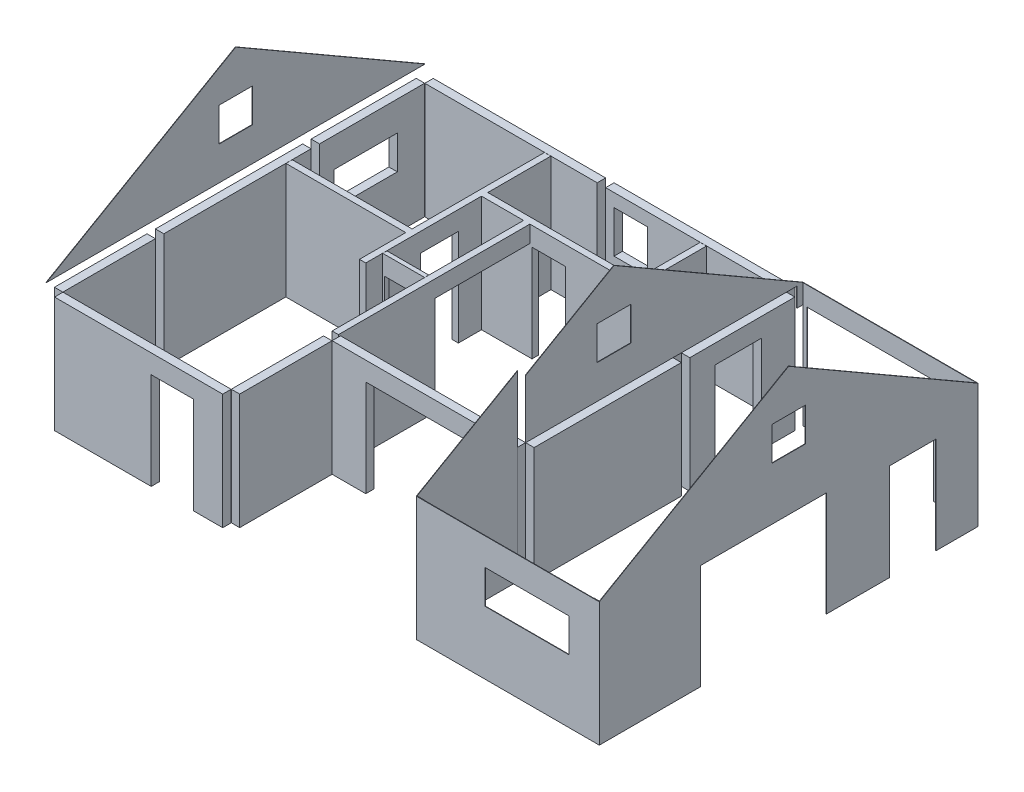
SolidWorks part; units mm, degrees
ref_plane "Спереди" through (0, 0, 0) normal (0, 0, 1) x (1, 0, 0)
ref_plane "Сверху" through (0, 0, 0) normal (0, 1, 0) x (1, 0, 0)
ref_plane "Справа" through (0, 0, 0) normal (1, 0, 0) x (0, 0, -1)
sketch "Эскиз1" plane through (0, 0, 0) normal (0, 1, 0) x (1, 0, 0)
  line L0 (9000, -6600) -> (4400, -6600) construction
  line L1 (0, 0) -> (9000, 0) construction
  line L2 (0, 0) -> (0, -8800) construction
  line L3 (0, -9000) -> (4400, -9000) construction
  line L4 (9000, 0) -> (9000, -6600) construction
  line L5 (4400, -6600) -> (4400, -9000) construction
  line L6 (8800, -203) -> (9000, -203)
  line L7 (203, 0) -> (4300, 0)
  line L8 (203, 0) -> (203, -200)
  line L9 (203, -200) -> (4300, -200)
  line L12 (0, -200) -> (0, -2700)
  line L14 (200, -200) -> (200, -2700)
  line L15 (203, -9000) -> (2500, -9000)
  line L16 (203, -9000) -> (203, -8800)
  line L17 (203, -8800) -> (2500, -8800)
  line L19 (4400, -8797) -> (4200, -8797)
  line L20 (4400, -8797) -> (4400, -6603)
  line L22 (4200, -8797) -> (4200, -6603)
  line L24 (9000, -203) -> (9000, -1000)
  line L26 (8800, -203) -> (8800, -1000)
  line L27 (8797, -6600) -> (7597, -6600)
  line L28 (8797, -6600) -> (8797, -6400)
  line L29 (8797, -6400) -> (7597, -6400)
  line L31 (2500, -8800) -> (2500, -9000)
  line L32 (3500, -8800) -> (3500, -9000)
  line L33 (3500, -8800) -> (4200, -8800)
  line L34 (3500, -9000) -> (4200, -9000)
  line L35 (5597, -6400) -> (5597, -6600)
  line L36 (7597, -6400) -> (7597, -6600)
  line L37 (5597, -6400) -> (4400, -6400)
  line L38 (5597, -6600) -> (4400, -6600)
  line L39 (8800, -1000) -> (9000, -1000)
  line L41 (8800, -2100) -> (9000, -2100)
  line L42 (8800, -2100) -> (8800, -2700)
  line L43 (9000, -2100) -> (9000, -2700)
  line L47 (4200, -6400) -> (4350, -6400)
  line L83 (4200, -6603) -> (4400, -6603)
  line L92 (4200, -4100) -> (4350, -4100)
  line L93 (4200, -4100) -> (4200, -6400)
  line L94 (4350, -4100) -> (4350, -6400)
  line L100 (200, -8800) -> (0, -8800)
  line L101 (4200, -8800) -> (4200, -9000)
  line L102 (4400, -6400) -> (4400, -6600)
  line L103 (8800, -6400) -> (9000, -6400)
  line L104 (0, -200) -> (200, -200)
  line L108 (0, -4500) -> (0, -6400)
  line L109 (200, -4500) -> (200, -6400)
  line L110 (8800, 0) -> (8800, -200)
  line L111 (4300, 0) -> (4300, -200)
  line L113 (4500, 0) -> (4500, -200)
  line L114 (4500, 0) -> (8800, 0)
  line L115 (4500, -200) -> (8800, -200)
  line L116 (0, -9000) -> (0, -8800) construction
  line L117 (-6170.9643, 0) -> (12200, 0) construction
  line L118 (0, 1882.3698) -> (0, -11726.3327) construction
  line L119 (-6170.9643, -4500) -> (10764.3505, -4500) construction
  line L120 (1000, -4500) -> (2250, -4500) construction
  line L121 (-6170.9643, -9000) -> (12200, -9000) construction
  line L122 (1000, -4500) -> (1000, -4600) construction
  line L123 (1000, -4600) -> (2250, -4600) construction
  line L124 (2250, -4500) -> (2250, -4600) construction
  line L125 (1000, -4500) -> (2250, -4600) construction
  line L126 (1000, -4600) -> (2250, -4500) construction
  line L131 (0, -2700) -> (200, -2700)
  line L132 (0, -2900) -> (0, -4500)
  line L137 (3050, -203) -> (3200, -203)
  line L138 (3050, -203) -> (3050, -2400)
  line L139 (3050, -2400) -> (3200, -2400)
  line L140 (3200, -203) -> (3200, -1700)
  line L141 (3050, -203) -> (3200, -2400) construction
  line L142 (3050, -2400) -> (3200, -203) construction
  line L143 (3050, -3300) -> (3200, -3300)
  line L144 (3050, -3300) -> (3050, -3350)
  line L145 (3050, -4600) -> (3200, -4600)
  line L146 (3200, -3300) -> (3200, -4600)
  line L147 (3050, -3300) -> (3200, -4600) construction
  line L148 (3050, -4600) -> (3200, -3300) construction
  line L149 (4150, -4100) -> (4197, -4100)
  line L150 (4150, -4100) -> (4150, -4200)
  line L151 (4150, -4200) -> (4197, -4200)
  line L152 (4197, -4100) -> (4197, -4200)
  line L153 (4150, -4100) -> (4197, -4200) construction
  line L154 (4150, -4200) -> (4197, -4100) construction
  line L155 (203, -3350) -> (3050, -3350)
  line L156 (203, -3350) -> (203, -3500)
  line L157 (203, -3500) -> (3050, -3500)
  line L159 (203, -3350) -> (3050, -3500) construction
  line L160 (203, -3500) -> (3050, -3350) construction
  line L161 (6400, -3500) -> (8800, -3500) construction
  line L162 (4400, 2182.3698) -> (4400, -11426.3327) construction
  line L163 (5200, -1700) -> (6750, -1700)
  line L164 (9000, 2182.3698) -> (9000, -11265.4622) construction
  line L165 (5200, -1700) -> (5200, -1850)
  line L166 (5200, -1850) -> (6900, -1850)
  line L167 (6900, -1700) -> (6900, -1850)
  line L168 (5200, -1700) -> (6900, -1850) construction
  line L169 (5200, -1850) -> (6900, -1700) construction
  line L170 (5800, -2800) -> (8797, -2800) construction
  line L171 (5800, -2800) -> (5800, -2900) construction
  line L172 (5800, -2900) -> (8797, -2900) construction
  line L173 (8797, -2800) -> (8797, -2900) construction
  line L174 (5800, -2800) -> (8797, -2900) construction
  line L175 (5800, -2900) -> (8797, -2800) construction
  line L176 (6750, -203) -> (6900, -203)
  line L177 (6750, -203) -> (6750, -1700)
  line L179 (6900, -203) -> (6900, -1700)
  line L180 (6750, -203) -> (6900, -1700) construction
  line L181 (6750, -1700) -> (6900, -203) construction
  line L186 (3200, -1700) -> (4400, -1700)
  line L188 (3200, -1850) -> (4400, -1850)
  line L189 (4400, -1700) -> (4400, -1850)
  line L190 (3200, -1700) -> (4400, -1850) construction
  line L191 (3200, -1850) -> (4400, -1700) construction
  line L192 (5800, -2900) -> (6400, -2900) construction
  line L193 (5800, -2900) -> (5800, -3500) construction
  line L194 (5800, -3500) -> (6400, -3500) construction
  line L195 (6400, -2900) -> (6400, -3500) construction
  line L196 (5800, -2900) -> (6400, -3500) construction
  line L197 (5800, -3500) -> (6400, -2900) construction
  line L198 (12200, 0) -> (12200, -9000) construction
  line L199 (5350, -4400) -> (5800, -3500) construction
  line L204 (3203, -4100) -> (3250, -4100)
  line L205 (3203, -4100) -> (3203, -4200)
  line L206 (3203, -4200) -> (3250, -4200)
  line L207 (3250, -4100) -> (3250, -4200)
  line L208 (3203, -4100) -> (3250, -4200) construction
  line L209 (3203, -4200) -> (3250, -4100) construction
  line L210 (4350, -4400) -> (5350, -4400) construction
  line L211 (4350, -4400) -> (4350, -6400) construction
  line L212 (4350, -6400) -> (5350, -6400) construction
  line L213 (5350, -4400) -> (5350, -6400) construction
  line L214 (4350, -4400) -> (5350, -6400) construction
  line L215 (4350, -6400) -> (5350, -4400) construction
  line L216 (3200, -1850) -> (3200, -2400)
  line L217 (0, -2900) -> (200, -2900)
  line L218 (200, -2900) -> (200, -4500)
  line L219 (0, -6400) -> (200, -6400)
  line L220 (0, -6600) -> (0, -8800)
  line L221 (0, -6600) -> (200, -6600)
  line L222 (200, -6600) -> (200, -8800)
  line L223 (3050, -3500) -> (3050, -4600)
  line L224 (8800, -2700) -> (9000, -2700)
  line L225 (8800, -2900) -> (8800, -6400)
  line L226 (8800, -2900) -> (9000, -2900)
  line L227 (9000, -2900) -> (9000, -6400)
  point P14 (3226.5, -4150)
  point P17 (7298.5, -2850)
  point P41 (1625, -4550)
  point P52 (3125, -1301.5)
  point P62 (3125, -3950)
  point P67 (4173.5, -4150)
  point P72 (1626.5, -3425)
  point P103 (3800, -1775)
  point P104 (6825, -951.5)
  point P105 (4150, -4150)
  point P108 (6050, -1775)
  point P120 (6750, -951.5)
  point P122 (6100, -3200)
  point P127 (4850, -5400)
  dimension "D2" = 6600
  dimension "D3" = 9000
  dimension "D4" = 200
  dimension "D5" = 3
  dimension "D6" = 3
  dimension "D7" = 3
  dimension "D8" = 9000
  dimension "D9" = 200
  dimension "D10" = 3
  dimension "D11" = 3
  dimension "D12" = 700
  dimension "D13" = 50
  dimension "D14" = 4500
  dimension "D15" = 4000
  dimension "D16" = 100
  dimension "D17" = 800
  dimension "D18" = 4400
  dimension "D19" = 4600
  dimension "D20" = 1000
  dimension "D21" = 800
  dimension "D22" = 2000
  dimension "D23" = 1200
  dimension "D24" = 1100
  dimension "D25" = 3
  dimension "D26" = 200
  dimension "D27" = 1000
  dimension "D29" = 200
  dimension "D30" = 4500
  dimension "D31" = 3
  dimension "D32" = 200
  dimension "D33" = 3
  dimension "D34" = 900
  dimension "D35" = 3
  dimension "D36" = 900
  dimension "D37" = 50
  dimension "D38" = 150
  dimension "D39" = 100
  dimension "D40" = 3
  dimension "D41" = 2850
  dimension "D42" = 3150
  dimension "D43" = 1250
  dimension "D44" = 200
  dimension "D46" = 3550
  dimension "D47" = 1500
  dimension "D48" = 800
  dimension "D49" = 1900
  dimension "D50" = 950
  dimension "D51" = 3
  dimension "D53" = 800
  dimension "D54" = 3
  dimension "D55" = 4450
  dimension "D56" = 3500
  dimension "D57" = 2400
  dimension "D58" = 3000
  dimension "D59" = 1400
  dimension "D60" = 2650
  dimension "D61" = 600
  dimension "D63" = 2900
  dimension "D64" = 2300
  dimension "D65" = 1247
  dimension "D66" = 3200
  dimension "D67" = 2000
  dimension "D68" = 1000
  dimension "D72" = 200
extrude "Бобышка-Вытянуть3" add sketch "Эскиз1" along normal blind 2750 contours L155 | L42 L103 L43 L41 | L26 L39 L24 L6 | L113 L115 L110 L114 | L216 L188 L189 L186 L140 L137 L138 L139 | L179 L176 L177 L163 L165 L166 L167 | L157 L223 L145 L146 L143 L144 L155 L156 | L108 L219 L109 L218 L217 L132 | L222 L221 L220 L100 | L144 L145 L146 L143 | L140 L139 L138 L137 | L27 L36 L29 L28 | L8 L9 L111 L7 | L14 L131 L12 L104 | L100 L108 L132 L217 L218 L109 | L47 L94 L92 L93 | L35 L38 L102 L37 | L171 L172 L173 L170 | L19 L22 L83 L20 | L32 L34 L101 L33 | L15 L31 L17 L16 | L122 L120 L124 L123 | L205 L204 L207 L206 | L150 L149 L152 L151 | L165 L163 L167 L166 | L103 L227 L226 L225 region at (8900, 0, 601.5) region at (8900, 0, 2400) region at (100, 0, 7700) region at (100, 0, 4650) region at (6650, 0, 100) region at (3125, 0, 228.7863) region at (3125, 0, 3332.668) region at (5975, 0, 1723.6698)
sketch "Эскиз2" plane through (0, 0, 0) normal (-1, 0, 0) x (0, 0, 1)
  line L2 (850, 1250) -> (2350, 1250)
  line L3 (850, 1250) -> (850, 2050)
  line L4 (850, 2050) -> (2350, 2050)
  line L5 (2350, 1250) -> (2350, 2050)
  line L7 (200, 0) -> (2700, 0) construction
  line L8 (3350, 2750) -> (3350, 0) construction
  dimension "D1" = 1500
  dimension "D2" = 800
  dimension "D3" = 1250
  dimension "D4" = 1000
extrude "Вырез-Вытянуть2" cut sketch "Эскиз2" against normal blind 250
sketch "Эскиз3" plane through (0, 0, 0) normal (0, 0, -1) x (-1, 0, 0)
  line L0 (-4500, 0) -> (-8800, 0) construction
  line L8 (-5500, 2440) -> (-4700, 2440)
  line L9 (-5500, 2440) -> (-5500, 1440)
  line L10 (-5500, 1440) -> (-4700, 1440)
  line L11 (-4700, 2440) -> (-4700, 1440)
  line L15 (-4500, 2750) -> (-4500, 0) construction
  dimension "D1" = 200
  dimension "D2" = 2440
  dimension "D3" = 800
  dimension "D4" = 1000
  dimension "D5" = 1440
extrude "Вырез-Вытянуть3" cut sketch "Эскиз3" against normal blind 593
sketch "Эскиз4" plane through (0, 2750, 0) normal (0, 1, 0) x (1, 0, 0)
  line L6 (3203, -4100) -> (3250, -4100) construction
  line L7 (3226.5, -4100) -> (4173.5, -4100)
  line L8 (3226.5, -4100) -> (3226.5, -4200)
  line L9 (3226.5, -4200) -> (4173.5, -4200)
  line L10 (4173.5, -4100) -> (4173.5, -4200)
  line L11 (4150, -4200) -> (4197, -4200) construction
  line L13 (3050, -2346.4504) -> (3200, -2346.4504)
  line L14 (3050, -2346.4504) -> (3050, -3325)
  line L15 (3050, -3325) -> (3200, -3325)
  line L16 (3200, -2346.4504) -> (3200, -3325)
  line L19 (4249.5007, -1700) -> (5402.0861, -1700)
  line L20 (4249.5007, -1700) -> (4249.5007, -1850)
  line L21 (4249.5007, -1850) -> (5402.0861, -1850)
  line L22 (5402.0861, -1700) -> (5402.0861, -1850)
  line L24 (5200, -1850) -> (6900, -1850) construction
  line L29 (3050, -203) -> (3050, -2400) construction
  line L30 (5597, -6400) -> (4400, -6400) construction
  line L31 (5423.0031, -6400) -> (7690.4362, -6400)
  line L32 (5423.0031, -6400) -> (5423.0031, -6600)
  line L33 (5423.0031, -6600) -> (7690.4362, -6600)
  line L34 (7690.4362, -6400) -> (7690.4362, -6600)
  line L35 (8797, -6600) -> (7597, -6600) construction
  line L36 (8800, -203) -> (8800, -1000) construction
  line L37 (8800, -900.8258) -> (9000, -900.8258)
  line L38 (8800, -900.8258) -> (8800, -2153.976)
  line L39 (8800, -2153.976) -> (9000, -2153.976)
  line L40 (9000, -900.8258) -> (9000, -2153.976)
  line L41 (9000, -2100) -> (9000, -2700) construction
  line L42 (3500, -9000) -> (4200, -9000) construction
  line L43 (2379.0159, -8797) -> (3597.5552, -8797)
  line L44 (2379.0159, -8797) -> (2379.0159, -9000)
  line L45 (2379.0159, -9000) -> (3597.5552, -9000)
  line L46 (3597.5552, -8797) -> (3597.5552, -9000)
  line L47 (3200, -1850) -> (3200, -2400) construction
  line L48 (3200, -1700) -> (4400, -1700) construction
extrude "Бобышка-Вытянуть4" add sketch "Эскиз4" against normal offset from surface (450 mm away) 2300 up to face at (8900, 0, 601.5)
ref_plane "Плоскость1" through (13000, 0, 0) normal (1, 0, 0) x (0, 0, -1)
sketch "Эскиз5" plane through (13000, 0, 0) normal (1, 0, 0) x (0, 0, -1)
  line L0 (-4500, 5721.2813) -> (-4500, -150) construction
  line L1 (-6600, -150) -> (0, -150) construction
  line L2 (-4500, 5548.0762) -> (-9000, 2950)
  line L3 (-9000, 2950) -> (-9000, 0)
  line L5 (0, 2950) -> (0, 0)
  line L6 (-4500, 5548.0762) -> (0, 2950)
  line L7 (-8800, 0) -> (-9000, 0) construction
  line L8 (-9000, 0) -> (-8750, 0) construction
  line L9 (-9000, 0) -> (0, 0)
extrude "Бобышка-Вытянуть5" add sketch "Эскиз5" along normal blind 150 separate body
sketch "Эскиз6" plane through (13000, 0, 0) normal (1, 0, 0) x (0, 0, -1)
  line L0 (-9000, 0) -> (0, 0) construction
  line L1 (-1000, 2300) -> (-2100, 2300)
  line L2 (-1000, 2300) -> (-1000, 0)
  line L3 (-1000, 0) -> (-2100, 0)
  line L4 (-2100, 2300) -> (-2100, 0)
  line L5 (0, 2494.3376) -> (50, 2494.3376) construction
  line L6 (-6600, -150) -> (-3600, -150)
  line L7 (-6600, -150) -> (-6600, 2494.3376)
  line L8 (-6600, 2494.3376) -> (-3600, 2494.3376)
  line L9 (-3600, -150) -> (-3600, 2494.3376)
  dimension "D1" = 3000
  dimension "D2" = 1100
extrude "Вырез-Вытянуть5" cut sketch "Эскиз6" along normal blind 670
sketch "Эскиз8" plane through (0, 0, 0) normal (-1, 0, 0) x (0, 0, 1)
  line L0 (4500, 5548.0762) -> (0, 2950)
  line L1 (0, 2950) -> (9000, 2950)
  line L2 (9000, 2950) -> (4500, 5548.0762)
  line L3 (4500, 5548.0762) -> (4500, 2950) construction
  line L4 (2350, 1250) -> (2350, 2050) construction
  line L5 (4100, 4550) -> (4900, 4550)
  line L6 (4100, 4550) -> (4100, 3750)
  line L7 (4100, 3750) -> (4900, 3750)
  line L8 (4900, 4550) -> (4900, 3750)
  dimension "D1" = 800
extrude "Бобышка-Вытянуть8" add sketch "Эскиз8" against normal blind 10 separate body
sketch "Эскиз9" plane through (9000, 0, 0) normal (1, 0, 0) x (0, 0, -1)
  line L0 (-6600, 0) -> (-6600, 2950)
  line L1 (-6600, 2750) -> (-6600, 0) construction
  line L2 (-6600, 2950) -> (0, 2950)
  line L3 (0, 2950) -> (-4500, 5548.0762)
  line L4 (-4500, 5548.0762) -> (-9000, 2950)
  line L5 (-9000, 2950) -> (-9000, 0)
  line L6 (-9000, 0) -> (-6600, 0)
extrude "Бобышка-Вытянуть9" add sketch "Эскиз9" against normal blind 200 separate body
sketch "Эскиз10" plane through (0, 0, 0) normal (0, -1, 0) x (1, 0, 0)
  line L0 (13000, 9000) -> (13000, 6600) construction
  line L1 (9000, 9000) -> (13000, 9000)
  line L2 (9000, 9000) -> (9000, 8850)
  line L3 (9000, 8850) -> (13000, 8850)
  line L4 (13000, 9000) -> (13000, 8850)
  line L5 (13150, 9000) -> (13000, 9000) construction
  line L6 (9000, 6600) -> (9000, 0) construction
  line L7 (13000, 0) -> (12100, 0)
  line L8 (13000, 0) -> (13000, 150)
  line L9 (13000, 150) -> (12100, 150)
  line L10 (12100, 0) -> (12100, 150)
  line L11 (9000, 150) -> (9100, 150)
  line L12 (9000, 150) -> (9000, 0)
  line L13 (9000, 0) -> (9100, 0)
  line L14 (9100, 150) -> (9100, 0)
extrude "Бобышка-Вытянуть10" add sketch "Эскиз10" against normal up to vertex (2950 mm away) up to point (9000, 2950, 9000)
sketch "Эскиз11" plane through (0, 0, 6400) normal (0, 0, -1) x (-1, 0, 0)
  line L1 (-7597, 2300) -> (-5200, 2300)
  line L2 (-7597, 2300) -> (-7597, -335.5255)
  line L3 (-7597, -335.5255) -> (-5200, -335.5255)
  line L4 (-5200, 2300) -> (-5200, -335.5255)
  line L6 (-2500, 2300) -> (-3500, 2300)
  line L7 (-2500, 2300) -> (-2500, -123.1481)
  line L8 (-2500, -123.1481) -> (-3500, -123.1481)
  line L9 (-3500, 2300) -> (-3500, -123.1481)
  line L11 (-10431.0972, 2300) -> (-12431.0972, 2300)
  line L12 (-10431.0972, 2300) -> (-10431.0972, 1500)
  line L13 (-10431.0972, 1500) -> (-12431.0972, 1500)
  line L14 (-12431.0972, 2300) -> (-12431.0972, 1500)
  dimension "D1" = 2000
  dimension "D2" = 800
  dimension "D3" = 2397
extrude "Вырез-Вытянуть6" cut sketch "Эскиз11" against normal blind 5123
sketch "Эскиз12" plane through (0, 0, 0) normal (-1, 0, 0) x (0, 0, 1)
  line L0 (2424.8711, 2950) -> (2424.8711, 4350) construction
  line L1 (0, 2950) -> (9000, 2950) construction
  line L2 (4500, 5548.0762) -> (0, 2950) construction
  line L3 (2424.8711, 4350) -> (3290.8965, 4850) construction
  line L4 (3290.8965, 4850) -> (5709.1035, 4850) construction
  line L5 (9000, 2950) -> (4500, 5548.0762) construction
  line L6 (5709.1035, 4850) -> (6575.1289, 4350) construction
  line L7 (6575.1289, 4350) -> (6575.1289, 2950) construction
  line L8 (4500, 5548.0762) -> (4500, 4850) construction
  dimension "D1" = 1900
  dimension "D2" = 2418.2069
  dimension "D3" = 1400
  dimension "D4" = 4150.2577
extrude "Вырез-Вытянуть7" cut sketch "Эскиз8<2>" against normal blind 16606 contours L5 L8 L7 L6
sketch "Эскиз8<2>" plane through (0, 0, 0) normal (-1, 0, 0) x (0, 0, 1) same geometry as "Эскиз8"
sketch "Эскиз13" plane through (0, 0, 0) normal (-1, 0, 0) x (0, 0, 1)
  line L0 (4500, 5548.0762) -> (0, 2950)
  line L1 (0, 2950) -> (0, 0)
  line L2 (0, 0) -> (9000, 0)
  line L3 (9000, 2950) -> (9000, 0) construction
  line L4 (4500, 5548.0762) -> (9000, 2950)
  line L5 (9000, 2950) -> (9000, 0)
  line L7 (4100, 4550) -> (4900, 4550)
  line L8 (4100, 4550) -> (4100, 3750)
  line L9 (4100, 3750) -> (4900, 3750)
  line L10 (4900, 4550) -> (4900, 3750)
  line L11 (850, 2050) -> (2350, 2050)
  line L12 (850, 2050) -> (850, 1250)
  line L13 (850, 1250) -> (2350, 1250)
  line L14 (2350, 2050) -> (2350, 1250)
sketch "Эскиз16" plane through (13150, 0, 0) normal (1, 0, 0) x (0, 0, -1)
  line L0 (-150, 2950) -> (-150, 0) construction
  line L1 (0, 2950) -> (-150, 2950)
  line L2 (0, 2950) -> (0, 2494.3376)
  line L3 (0, 2494.3376) -> (-150, 2494.3376)
  line L4 (-150, 2950) -> (-150, 2494.3376)
  line L5 (-3600, 2494.3376) -> (-6600, 2494.3376) construction
extrude "Бобышка-Вытянуть16" add sketch "Эскиз16" against normal blind 4160
sketch "Эскиз17" plane through (0, 0, 4100) normal (0, 0, -1) x (-1, 0, 0)
  line L0 (-4200, 2750) -> (-4200, 0) construction
  line L1 (-4350, 2750) -> (-4200, 2750)
  line L2 (-4350, 2750) -> (-4350, 2350)
  line L3 (-4350, 2350) -> (-4200, 2350)
  line L4 (-4200, 2750) -> (-4200, 2350)
  dimension "D1" = 400
extrude "Бобышка-Вытянуть17" add sketch "Эскиз17" along normal up to surface (2250 mm away) up to face at (4925, 1262.5, 1850)
sketch "Эскиз18" plane through (0, 2750, 0) normal (0, 1, 0) x (1, 0, 0)
  line L0 (9000, -4500) -> (9000, -9000) construction
  line L1 (8644.5298, 46.0605) -> (8990, 46.0605)
  line L2 (8644.5298, 46.0605) -> (8644.5298, -6600)
  line L3 (8644.5298, -6600) -> (8990, -6600)
  line L4 (8990, 46.0605) -> (8990, -6600)
  line L5 (8797, -6600) -> (4400, -6600) construction
  line L6 (13000, -9000) -> (9000, -9000) construction
  line L7 (9392.4652, -10) -> (13140, -10)
  line L8 (9392.4652, -10) -> (9392.4652, -8990)
  line L9 (9392.4652, -8990) -> (13140, -8990)
  line L10 (13140, -10) -> (13140, -8990)
  line L11 (13150, -4500) -> (13150, -9000) construction
  line L12 (9000, 0) -> (13000, 0) construction
  dimension "D1" = 10
  dimension "D2" = 10
  dimension "D3" = 10
  dimension "D4" = 10
extrude "Вырез-Вытянуть8" cut sketch "Эскиз18" along normal blind 5414
sketch "Эскиз19" plane through (0, 0, 0) normal (0, -1, 0) x (1, 0, 0)
  line L0 (8990, 6600) -> (8800, 6600) construction
  line L1 (8810, 6600) -> (11709.562, 6600)
  line L2 (8810, 6600) -> (8810, 8990)
  line L3 (8810, 8990) -> (13140, 8990)
  line L4 (13140, 6600) -> (13140, 8990)
  line L5 (8797, 6600) -> (4400, 6600) construction
  line L6 (8800, 6600) -> (8800, 9000) construction
  line L7 (8800, 9000) -> (9000, 9000) construction
  line L8 (13140, 8990) -> (13140, 10) construction
  line L9 (9000, 10) -> (13140, 10)
  line L10 (13140, 10) -> (13140, 6600)
  line L11 (13140, 10) -> (9392.4652, 10) construction
  line L12 (9000, 0) -> (9000, 150) construction
  line L13 (9000, 10) -> (9000, 150)
  line L14 (9000, 150) -> (11709.562, 6600)
  dimension "D1" = 10
  dimension "D2" = 10
extrude "Вырез-Вытянуть9" cut sketch "Эскиз19" against normal blind 5663
